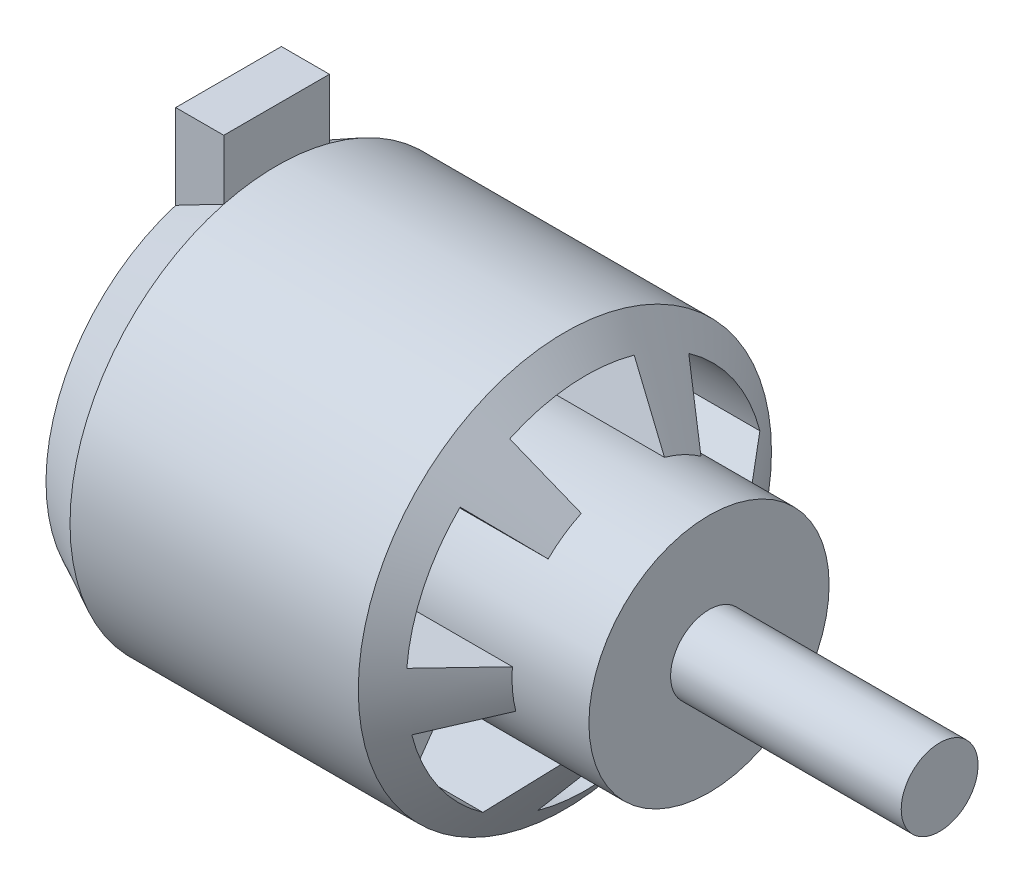
SolidWorks part; units mm, degrees
ref_plane "Front" through (0, 0, 0) normal (0, 0, 1) x (1, 0, 0)
ref_plane "Top" through (0, 0, 0) normal (0, 1, 0) x (1, 0, 0)
ref_plane "Right" through (0, 0, 0) normal (1, 0, 0) x (0, 0, -1)
sketch "Sketch1" plane through (0, 0, 0) normal (0, 0, 1) x (1, 0, 0)
  line L0 (0, 0) -> (0, 19)
  line L1 (0, 19) -> (5, 21.5)
  line L2 (5, 21.5) -> (35, 21.5)
  line L3 (35, 21.5) -> (42, 12.5)
  line L4 (42, 12.5) -> (50, 12.5)
  line L5 (50, 12.5) -> (50, 4)
  line L6 (50, 4) -> (74, 4)
  line L7 (74, 4) -> (74, 0)
  line L8 (0, 0) -> (74, 0) construction
  line L9 (0, 0) -> (74, 0)
  dimension "D1" = 38
  dimension "D2" = 43
  dimension "D3" = 5
  dimension "D4" = 42
  dimension "D5" = 30
  dimension "D6" = 25
  dimension "D7" = 8
  dimension "D8" = 24
  dimension "D9" = 8
revolve "Revolve1" add sketch "Sketch1" angle 360 about L8
sketch "Sketch2" plane through (50, 0, 0) normal (1, 0, 0) x (0, 0, -1)
  line L0 (18.6304, -1.6116) -> (12.4535, -1.0773)
  line L1 (13.078, -13.3662) -> (8.742, -8.9346)
  line L2 (7.9195, -16.9402) -> (5.2938, -11.3237)
  line L3 (-5.0365, -18.009) -> (-3.3666, -12.0381)
  line L4 (-10.7109, -15.3286) -> (-7.1597, -10.2464)
  line L5 (-18.1145, -4.6428) -> (-12.1086, -3.1035)
  line L6 (-18.6304, 1.6116) -> (-12.4535, 1.0773)
  line L7 (-13.078, 13.3662) -> (-8.742, 8.9346)
  line L8 (-7.9195, 16.9402) -> (-5.2938, 11.3237)
  line L9 (5.0365, 18.009) -> (3.3666, 12.0381)
  line L10 (10.7109, 15.3286) -> (7.1597, 10.2464)
  line L11 (18.1145, 4.6428) -> (12.1086, 3.1035)
  circle A0 centre (0, 0) radius 12.5 construction
  arc A1 (8.742, -8.9346) -> (12.4535, -1.0773) centre (0, 0) ccw
  arc A2 (-5.0365, -18.009) -> (7.9195, -16.9402) centre (0, 0) ccw
  arc A3 (-3.3666, -12.0381) -> (5.2938, -11.3237) centre (0, 0) ccw
  circle A4 centre (0, 0) radius 18.7
  arc A5 (13.078, -13.3662) -> (18.6304, -1.6116) centre (0, 0) ccw
  arc A6 (-18.1145, -4.6428) -> (-10.7109, -15.3286) centre (0, 0) ccw
  arc A7 (-12.1086, -3.1035) -> (-7.1597, -10.2464) centre (0, 0) ccw
  arc A8 (-13.078, 13.3662) -> (-18.6304, 1.6116) centre (0, 0) ccw
  arc A9 (-8.742, 8.9346) -> (-12.4535, 1.0773) centre (0, 0) ccw
  arc A10 (5.0365, 18.009) -> (-7.9195, 16.9402) centre (0, 0) ccw
  arc A11 (3.3666, 12.0381) -> (-5.2938, 11.3237) centre (0, 0) ccw
  arc A12 (18.1145, 4.6428) -> (10.7109, 15.3286) centre (0, 0) ccw
  arc A13 (12.1086, 3.1035) -> (7.1597, 10.2464) centre (0, 0) ccw
  point P31 (0, 0)
  dimension "D2" = 13
  dimension "D1" = 2.8
  dimension "D3" = 6
extrude "Cut-Extrude1" cut sketch "Sketch2" against normal blind 20
sketch "Sketch3" plane through (0, 0, 0) normal (0, 1, 0) x (1, 0, 0)
  line L0 (0, 19) -> (0, -19) construction
  line L1 (0, 5.5) -> (5, 5.5)
  line L2 (0, 5.5) -> (0, -5.5)
  line L3 (0, -5.5) -> (5, -5.5)
  line L4 (5, 5.5) -> (5, -5.5)
  line L5 (5, -21.5) -> (5, 21.5) construction
  line L6 (5, 0) -> (0, 0) construction
  line L7 (5, -21.5) -> (35, -21.5) construction
  line L8 (35, 21.5) -> (5, 21.5) construction
  dimension "D1" = 11
extrude "Boss-Extrude1" add sketch "Sketch3" along normal blind 27
